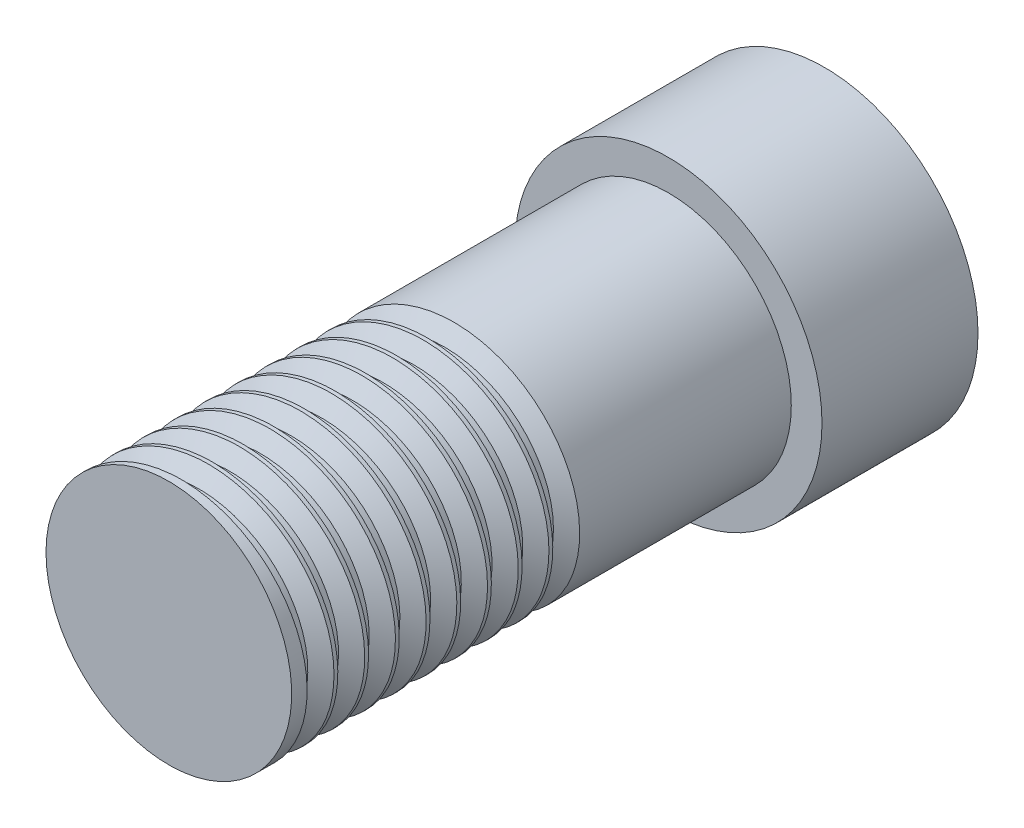
SolidWorks part; units mm, degrees
ref_plane "Front Plane" through (0, 0, 0) normal (0, 0, 1) x (1, 0, 0)
ref_plane "Top Plane" through (0, 0, 0) normal (0, 1, 0) x (1, 0, 0)
ref_plane "Right Plane" through (0, 0, 0) normal (1, 0, 0) x (0, 0, -1)
sketch "Sketch1" plane through (0, 0, 0) normal (0, 0, 1) x (1, 0, 0)
  circle A0 centre (0, 0) radius 2.5525
  circle A1 centre (0, 0) radius 5
  dimension "D1" = 5.105
  dimension "D2" = 10
extrude "Boss-Extrude1" add sketch "Sketch1" along normal blind 5.08 contours A1 | A0
sketch "Sketch2" plane through (0, 0, 5.08) normal (0, 0, 1) x (1, 0, 0)
  circle A0 centre (0, 0) radius 4
  dimension "D1" = 8
extrude "Boss-Extrude2" add sketch "Sketch2" along normal blind 1.27
thread "Thread1" pitch 1.27 method extrude profile "Thread Profile1" start angle 0, offset 0, length 5.2, pitch 1.27, diameter 5.105
ref_plane "Plane1" through (2.5525, 0, 0) normal (0, -1, 0) x (1, 0, 0)
sketch "Thread Profile1" plane through (2.5525, 0, 0) normal (0, -1, 0) x (1, 0, 0)
  line L0 (0, 0) -> (0, 1.27) construction
  line L11 (0, 0) -> (0, 1.1112)
  line L12 (0, 1.1112) -> (-0.6874, 0.7144)
  line L13 (-0.6874, 0.7144) -> (-0.6874, 0.3969)
  line L15 (-0.6874, 0.3969) -> (0, 0)
  line L17 (-0.6874, 0.5556) -> (0, 0.5556) construction
  point P2 (0, 0)
  dimension "Pitch" = 1.27
  dimension "Profile_Angle" = 60
  dimension "Profile_Land" = 0.3175
  dimension "Profile_Height" = 0.6874
sketch "Sketch4" plane through (0, 0, 6.35) normal (0, 0, 1) x (1, 0, 0)
  circle A0 centre (0, 0) radius 4
  dimension "D1" = 8
extrude "Boss-Extrude3" add sketch "Sketch4" along normal blind 15
thread "Thread2" pitch 1 method cut profile "Thread Profile3" start angle 0, offset 0, length 9, pitch 1, diameter 8
ref_plane "Plane3" through (-4, 0, 21.35) normal (0, -1, 0) x (-1, 0, 0)
sketch "Thread Profile3" plane through (-4, 0, 21.35) normal (0, -1, 0) x (-1, 0, 0)
  line L0 (0, 0) -> (0, 1) construction
  line L11 (0, 0) -> (0, 0.875)
  line L12 (0, 0.875) -> (-0.5413, 0.5625)
  line L13 (-0.5413, 0.5625) -> (-0.5413, 0.3125)
  line L15 (-0.5413, 0.3125) -> (0, 0)
  line L17 (-0.5413, 0.4375) -> (0, 0.4375) construction
  point P2 (0, 0)
  dimension "Pitch" = 1
  dimension "Profile_Angle" = 60
  dimension "Profile_Land" = 0.25
  dimension "Profile_Height" = 0.5413
